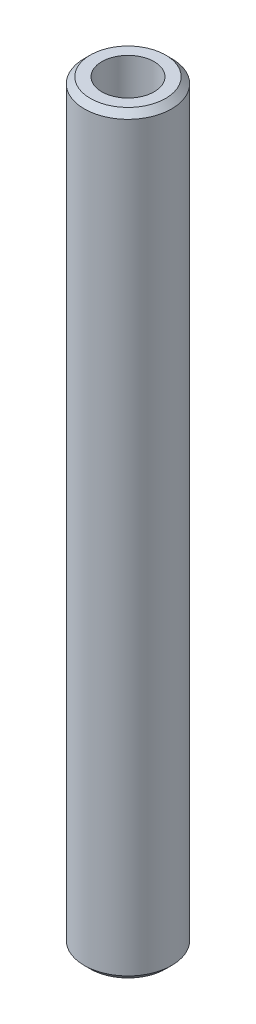
SolidWorks part; units mm, degrees
ref_plane "Front Plane" through (0, 0, 0) normal (0, 0, 1) x (1, 0, 0)
ref_plane "Top Plane" through (0, 0, 0) normal (0, 1, 0) x (1, 0, 0)
ref_plane "Right Plane" through (0, 0, 0) normal (1, 0, 0) x (0, 0, -1)
sketch "Sketch1" plane through (0, 0, 0) normal (0, 1, 0) x (1, 0, 0)
  circle A0 centre (0, 0) radius 30
  dimension "SHAFT_OD" = 60
extrude "Boss-Extrude1" add sketch "Sketch1" along normal blind 517.9862
sketch "Sketch2" plane through (0, 0, 0) normal (0, 1, 0) x (1, 0, 0)
  circle A0 centre (0, 0) radius 17.9821
  dimension "BORE_D" = 35.9643
extrude "Cut-Extrude1" cut sketch "Sketch2" along normal through all
chamfer "Chamfer1" distance 4.1499 angle 45 2 edges at (0, 517.9862, 30) (0, 0, 30)
